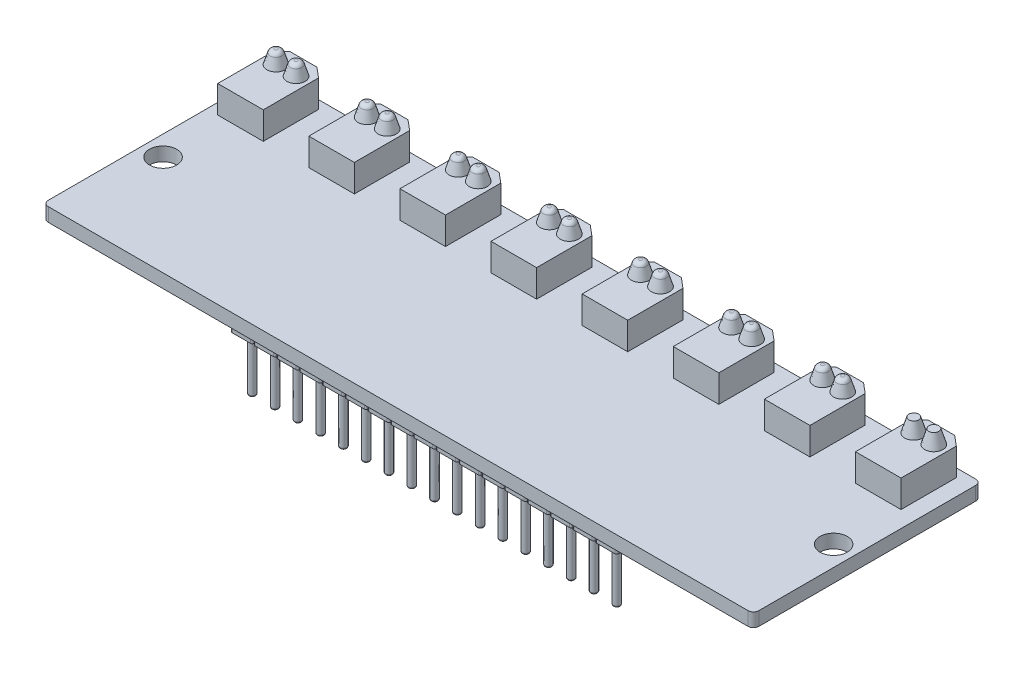
SolidWorks part; units mm, degrees
ref_plane "Front Plane" through (0, 0, 0) normal (0, 0, 1) x (1, 0, 0)
ref_plane "Top Plane" through (0, 0, 0) normal (0, 1, 0) x (1, 0, 0)
ref_plane "Right Plane" through (0, 0, 0) normal (1, 0, 0) x (0, 0, -1)
sketch "Sketch1" plane through (0, 0, 0) normal (0, 1, 0) x (1, 0, 0)
  line L1 (39, -12.5) -> (-39, -12.5)
  line L2 (39, -12.5) -> (39, 12.5)
  line L3 (39, 12.5) -> (-39, 12.5)
  line L4 (-39, -12.5) -> (-39, 12.5)
  line L5 (39, -12.5) -> (-39, 12.5) construction
  line L6 (39, 12.5) -> (-39, -12.5) construction
  point P0 (0, 0)
  dimension "D1" = 25
  dimension "D2" = 78
extrude "Boss-Extrude1" add sketch "Sketch1" along normal blind 1.5
fillet "Fillet1" radius 0.6 4 edges at (39, 0.75, 12.5) (39, 0.75, -12.5) (-39, 0.75, -12.5) (-39, 0.75, 12.5)
sketch "Sketch2" plane through (0, 1.5, 0) normal (0, 1, 0) x (1, 0, 0)
  line L0 (0, 0) -> (0, 12.5) construction
  line L1 (38.4, 12.5) -> (-38.4, 12.5) construction
  line L2 (-39, 11.9) -> (-39, -11.9) construction
  circle A0 centre (-36.8, -1.5) radius 1.5
  circle A1 centre (36.8, -1.5) radius 1.5
  dimension "D1" = 3
  dimension "D2" = 14
  dimension "D3" = 2.2
extrude "Cut-Extrude1" cut sketch "Sketch2" against normal blind 1.5
sketch "Sketch3" plane through (0, 1.5, 0) normal (0, 1, 0) x (1, 0, 0)
  line L0 (38.4, 12.5) -> (-38.4, 12.5) construction
  line L1 (-36.8668, 12.5) -> (-33.914, 12.5)
  line L2 (-37.8, 11.5668) -> (-37.8, 5.5)
  line L3 (-37.8, 5.5) -> (-32.8, 5.5)
  line L4 (-32.8, 11.5668) -> (-32.8, 5.5)
  line L5 (-37.4112, 11.9556) -> (-32.8, 5.5) construction
  line L6 (-37.8, 5.5) -> (-33.217, 11.9161) construction
  line L7 (-39, 11.9) -> (-39, -11.9) construction
  line L8 (-36.8668, 12.5) -> (-37.8, 11.5668)
  line L9 (-33.914, 12.5) -> (-32.8, 11.5668)
  line L10 (-22.8, 11.5668) -> (-22.8, 5.5)
  line L11 (-23.914, 12.5) -> (-22.8, 11.5668)
  line L12 (-26.8668, 12.5) -> (-23.914, 12.5)
  line L13 (-26.8668, 12.5) -> (-27.8, 11.5668)
  line L14 (-27.8, 11.5668) -> (-27.8, 5.5)
  line L15 (-27.8, 5.5) -> (-22.8, 5.5)
  line L16 (-12.8, 11.5668) -> (-12.8, 5.5)
  line L17 (-13.914, 12.5) -> (-12.8, 11.5668)
  line L18 (-16.8668, 12.5) -> (-13.914, 12.5)
  line L19 (-16.8668, 12.5) -> (-17.8, 11.5668)
  line L20 (-17.8, 11.5668) -> (-17.8, 5.5)
  line L21 (-17.8, 5.5) -> (-12.8, 5.5)
  line L22 (-2.8, 11.5668) -> (-2.8, 5.5)
  line L23 (-3.914, 12.5) -> (-2.8, 11.5668)
  line L24 (-6.8668, 12.5) -> (-3.914, 12.5)
  line L25 (-6.8668, 12.5) -> (-7.8, 11.5668)
  line L26 (-7.8, 11.5668) -> (-7.8, 5.5)
  line L27 (-7.8, 5.5) -> (-2.8, 5.5)
  line L28 (7.2, 11.5668) -> (7.2, 5.5)
  line L29 (6.086, 12.5) -> (7.2, 11.5668)
  line L30 (3.1332, 12.5) -> (6.086, 12.5)
  line L31 (3.1332, 12.5) -> (2.2, 11.5668)
  line L32 (2.2, 11.5668) -> (2.2, 5.5)
  line L33 (2.2, 5.5) -> (7.2, 5.5)
  line L34 (17.2, 11.5668) -> (17.2, 5.5)
  line L35 (16.086, 12.5) -> (17.2, 11.5668)
  line L36 (13.1332, 12.5) -> (16.086, 12.5)
  line L37 (13.1332, 12.5) -> (12.2, 11.5668)
  line L38 (12.2, 11.5668) -> (12.2, 5.5)
  line L39 (12.2, 5.5) -> (17.2, 5.5)
  line L40 (27.2, 11.5668) -> (27.2, 5.5)
  line L41 (26.086, 12.5) -> (27.2, 11.5668)
  line L42 (23.1332, 12.5) -> (26.086, 12.5)
  line L43 (23.1332, 12.5) -> (22.2, 11.5668)
  line L44 (22.2, 11.5668) -> (22.2, 5.5)
  line L45 (22.2, 5.5) -> (27.2, 5.5)
  line L46 (37.2, 11.5668) -> (37.2, 5.5)
  line L47 (36.086, 12.5) -> (37.2, 11.5668)
  line L48 (33.1332, 12.5) -> (36.086, 12.5)
  line L49 (33.1332, 12.5) -> (32.2, 11.5668)
  line L50 (32.2, 11.5668) -> (32.2, 5.5)
  line L51 (32.2, 5.5) -> (37.2, 5.5)
  point P0 (-35.3, 9)
  dimension "D1" = 5
  dimension "D2" = 7
  dimension "D3" = 0
  dimension "D4" = 1.2
  dimension "D5" = 8
extrude "Boss-Extrude2" add sketch "Sketch3" along normal blind 3
sketch "Sketch4" plane through (0, 4.5, 0) normal (0, 1, 0) x (1, 0, 0)
  line L0 (-37.8, 11.5668) -> (-37.8, 5.5) construction
  line L1 (-32.8, 5.5) -> (-32.8, 11.5668) construction
  line L2 (-37.8, 5.5) -> (-32.8, 5.5) construction
  line L3 (-37.8, 5.5) -> (-32.8, 5.5) construction
  circle A0 centre (-36.4, 10.4996) radius 1
  circle A1 centre (-34.2, 10.4996) radius 1
  circle A2 centre (-26.4, 10.4996) radius 1 construction
  circle A3 centre (-24.2, 10.4996) radius 1 construction
  circle A4 centre (-16.4, 10.4996) radius 1 construction
  circle A5 centre (-14.2, 10.4996) radius 1 construction
  circle A6 centre (-6.4, 10.4996) radius 1 construction
  circle A7 centre (-4.2, 10.4996) radius 1 construction
  circle A8 centre (3.6, 10.4996) radius 1 construction
  circle A9 centre (5.8, 10.4996) radius 1 construction
  circle A10 centre (13.6, 10.4996) radius 1 construction
  circle A11 centre (15.8, 10.4996) radius 1 construction
  circle A12 centre (23.6, 10.4996) radius 1 construction
  circle A13 centre (25.8, 10.4996) radius 1 construction
  circle A14 centre (33.6, 10.4996) radius 1 construction
  circle A15 centre (35.8, 10.4996) radius 1 construction
  circle A16 centre (-26.4, 10.4996) radius 1
  circle A17 centre (-24.2, 10.4996) radius 1
  circle A18 centre (-16.4, 10.4996) radius 1
  circle A19 centre (-14.2, 10.4996) radius 1
  circle A20 centre (-6.4, 10.4996) radius 1
  circle A21 centre (-4.2, 10.4996) radius 1
  circle A22 centre (3.6, 10.4996) radius 1
  circle A23 centre (5.8, 10.4996) radius 1
  circle A24 centre (13.6, 10.4996) radius 1
  circle A25 centre (15.8, 10.4996) radius 1
  circle A26 centre (23.6, 10.4996) radius 1
  circle A27 centre (25.8, 10.4996) radius 1
  circle A28 centre (33.6, 10.4996) radius 1
  circle A29 centre (35.8, 10.4996) radius 1
  dimension "D1" = 2
  dimension "D2" = 2
  dimension "D5" = 4.9996
  dimension "D6" = 4.9996
  dimension "D3" = 1.4
  dimension "D4" = 1.4
  dimension "D7" = 8
  dimension "D8" = 8
extrude "Boss-Extrude7" add sketch "Sketch4" along normal blind 1.5 draft 17
fillet "Fillet4" radius 0.5 14 edges at (-36.4, 6, -9.9582) (-34.2, 6, -9.9582) (-26.4, 6, -9.9582) (-24.2, 6, -9.9582) (-16.4, 6, -9.9582) (-14.2, 6, -9.9582) (-6.4, 6, -9.9582) (-4.2, 6, -9.9582) (25.8, 6, -9.9582) (23.6, 6, -9.9582) (15.8, 6, -9.9582) (13.6, 6, -9.9582) (5.8, 6, -9.9582) (3.6, 6, -9.9582)
sketch "Sketch5" plane through (0, 0, 0) normal (0, -1, 0) x (1, 0, 0)
  line L0 (38.4, -12.5) -> (-38.4, -12.5) construction
  line L1 (-22.5, 10.9) -> (-20.1, 10.9)
  line L2 (-22.5, 10.9) -> (-22.5, 8.5)
  line L3 (-22.5, 8.5) -> (-20.1, 8.5)
  line L4 (-20.1, 10.9) -> (-20.1, 8.5)
  line L5 (-22.5, 10.9) -> (-20.1, 8.5) construction
  line L6 (-22.5, 8.5) -> (-20.1, 10.9) construction
  line L7 (-20, 10.9) -> (-20, 8.5)
  line L8 (-17.6, 10.9) -> (-17.6, 8.5)
  line L9 (-20, 8.5) -> (-17.6, 8.5)
  line L10 (-17.5, 10.9) -> (-17.5, 8.5)
  line L11 (-15.1, 10.9) -> (-15.1, 8.5)
  line L12 (-17.5, 8.5) -> (-15.1, 8.5)
  line L13 (-15, 10.9) -> (-15, 8.5)
  line L14 (-12.6, 10.9) -> (-12.6, 8.5)
  line L15 (-15, 8.5) -> (-12.6, 8.5)
  line L16 (-12.5, 10.9) -> (-12.5, 8.5)
  line L17 (-10.1, 10.9) -> (-10.1, 8.5)
  line L18 (-12.5, 8.5) -> (-10.1, 8.5)
  line L19 (-10, 10.9) -> (-10, 8.5)
  line L20 (-7.6, 10.9) -> (-7.6, 8.5)
  line L21 (-10, 8.5) -> (-7.6, 8.5)
  line L22 (-7.5, 10.9) -> (-7.5, 8.5)
  line L23 (-5.1, 10.9) -> (-5.1, 8.5)
  line L24 (-7.5, 8.5) -> (-5.1, 8.5)
  line L25 (-5, 10.9) -> (-5, 8.5)
  line L26 (-2.6, 10.9) -> (-2.6, 8.5)
  line L27 (-5, 8.5) -> (-2.6, 8.5)
  line L28 (-2.5, 10.9) -> (-2.5, 8.5)
  line L29 (-0.1, 10.9) -> (-0.1, 8.5)
  line L30 (-2.5, 8.5) -> (-0.1, 8.5)
  line L31 (0, 10.9) -> (0, 8.5)
  line L32 (2.4, 10.9) -> (2.4, 8.5)
  line L33 (0, 8.5) -> (2.4, 8.5)
  line L34 (2.5, 10.9) -> (2.5, 8.5)
  line L35 (4.9, 10.9) -> (4.9, 8.5)
  line L36 (2.5, 8.5) -> (4.9, 8.5)
  line L37 (5, 10.9) -> (5, 8.5)
  line L38 (7.4, 10.9) -> (7.4, 8.5)
  line L39 (5, 8.5) -> (7.4, 8.5)
  line L40 (7.5, 10.9) -> (7.5, 8.5)
  line L41 (9.9, 10.9) -> (9.9, 8.5)
  line L42 (7.5, 8.5) -> (9.9, 8.5)
  line L43 (10, 10.9) -> (10, 8.5)
  line L44 (12.4, 10.9) -> (12.4, 8.5)
  line L45 (10, 8.5) -> (12.4, 8.5)
  line L46 (12.5, 10.9) -> (12.5, 8.5)
  line L47 (14.9, 10.9) -> (14.9, 8.5)
  line L48 (12.5, 8.5) -> (14.9, 8.5)
  line L49 (15, 10.9) -> (15, 8.5)
  line L50 (17.4, 10.9) -> (17.4, 8.5)
  line L51 (15, 8.5) -> (17.4, 8.5)
  line L52 (17.5, 10.9) -> (17.5, 8.5)
  line L53 (19.9, 10.9) -> (19.9, 8.5)
  line L54 (17.5, 8.5) -> (19.9, 8.5)
  line L55 (20, 10.9) -> (20, 8.5)
  line L56 (22.4, 10.9) -> (22.4, 8.5)
  line L57 (20, 8.5) -> (22.4, 8.5)
  line L58 (-20, 10.9) -> (-20, 8.5)
  line L59 (-17.6, 10.9) -> (-17.6, 8.5)
  line L60 (-20, 8.5) -> (-17.6, 8.5)
  line L61 (-20, 10.9) -> (-17.6, 10.9)
  line L62 (-17.5, 10.9) -> (-17.5, 8.5)
  line L63 (-15.1, 10.9) -> (-15.1, 8.5)
  line L64 (-17.5, 8.5) -> (-15.1, 8.5)
  line L65 (-17.5, 10.9) -> (-15.1, 10.9)
  line L66 (-15, 10.9) -> (-15, 8.5)
  line L67 (-12.6, 10.9) -> (-12.6, 8.5)
  line L68 (-15, 8.5) -> (-12.6, 8.5)
  line L69 (-15, 10.9) -> (-12.6, 10.9)
  line L70 (-12.5, 10.9) -> (-12.5, 8.5)
  line L71 (-10.1, 10.9) -> (-10.1, 8.5)
  line L72 (-12.5, 8.5) -> (-10.1, 8.5)
  line L73 (-12.5, 10.9) -> (-10.1, 10.9)
  line L74 (-10, 10.9) -> (-10, 8.5)
  line L75 (-7.6, 10.9) -> (-7.6, 8.5)
  line L76 (-10, 8.5) -> (-7.6, 8.5)
  line L77 (-10, 10.9) -> (-7.6, 10.9)
  line L78 (-7.5, 10.9) -> (-7.5, 8.5)
  line L79 (-5.1, 10.9) -> (-5.1, 8.5)
  line L80 (-7.5, 8.5) -> (-5.1, 8.5)
  line L81 (-7.5, 10.9) -> (-5.1, 10.9)
  line L82 (-5, 10.9) -> (-5, 8.5)
  line L83 (-2.6, 10.9) -> (-2.6, 8.5)
  line L84 (-5, 8.5) -> (-2.6, 8.5)
  line L85 (-5, 10.9) -> (-2.6, 10.9)
  line L86 (-2.5, 10.9) -> (-2.5, 8.5)
  line L87 (-0.1, 10.9) -> (-0.1, 8.5)
  line L88 (-2.5, 8.5) -> (-0.1, 8.5)
  line L89 (-2.5, 10.9) -> (-0.1, 10.9)
  line L90 (0, 10.9) -> (0, 8.5)
  line L91 (2.4, 10.9) -> (2.4, 8.5)
  line L92 (0, 8.5) -> (2.4, 8.5)
  line L93 (0, 10.9) -> (2.4, 10.9)
  line L94 (2.5, 10.9) -> (2.5, 8.5)
  line L95 (4.9, 10.9) -> (4.9, 8.5)
  line L96 (2.5, 8.5) -> (4.9, 8.5)
  line L97 (2.5, 10.9) -> (4.9, 10.9)
  line L98 (5, 10.9) -> (5, 8.5)
  line L99 (7.4, 10.9) -> (7.4, 8.5)
  line L100 (5, 8.5) -> (7.4, 8.5)
  line L101 (5, 10.9) -> (7.4, 10.9)
  line L102 (7.5, 10.9) -> (7.5, 8.5)
  line L103 (9.9, 10.9) -> (9.9, 8.5)
  line L104 (7.5, 8.5) -> (9.9, 8.5)
  line L105 (7.5, 10.9) -> (9.9, 10.9)
  line L106 (10, 10.9) -> (10, 8.5)
  line L107 (12.4, 10.9) -> (12.4, 8.5)
  line L108 (10, 8.5) -> (12.4, 8.5)
  line L109 (10, 10.9) -> (12.4, 10.9)
  line L110 (12.5, 10.9) -> (12.5, 8.5)
  line L111 (14.9, 10.9) -> (14.9, 8.5)
  line L112 (12.5, 8.5) -> (14.9, 8.5)
  line L113 (12.5, 10.9) -> (14.9, 10.9)
  line L114 (15, 10.9) -> (15, 8.5)
  line L115 (17.4, 10.9) -> (17.4, 8.5)
  line L116 (15, 8.5) -> (17.4, 8.5)
  line L117 (15, 10.9) -> (17.4, 10.9)
  line L118 (17.5, 10.9) -> (17.5, 8.5)
  line L119 (19.9, 10.9) -> (19.9, 8.5)
  line L120 (17.5, 8.5) -> (19.9, 8.5)
  line L121 (17.5, 10.9) -> (19.9, 10.9)
  line L122 (20, 10.9) -> (20, 8.5)
  line L123 (22.4, 10.9) -> (22.4, 8.5)
  line L124 (20, 8.5) -> (22.4, 8.5)
  line L125 (20, 10.9) -> (22.4, 10.9)
  line L126 (-39, -11.9) -> (-39, 11.9) construction
  point P0 (-21.3, 9.7)
  dimension "D1" = 2.4
  dimension "D2" = 2.4
  dimension "D3" = 21
  dimension "D6" = 16.5
  dimension "D4" = 18
  dimension "D5" = 18
extrude "Boss-Extrude12" add sketch "Sketch5" along normal blind 2 contours L65 L10 L12 L11 | L69 L13 L15 L14 | L73 L16 L18 L17 | L77 L19 L21 L20 | L81 L22 L24 L23 | L61 L7 L9 L8 | L85 L25 L27 L26 | L89 L28 L30 L29 | L93 L31 L33 L32 | L97 L34 L36 L35 | L101 L37 L39 L38 | L105 L40 L42 L41 | L109 L43 L45 L44 | L113 L46 L48 L47 | L117 L49 L51 L50 | L121 L52 L54 L53 | L125 L55 L57 L56 region at (-18.8, 0, 9.7) region at (-16.3, 0, 9.7) region at (-13.8, 0, 9.7) region at (-11.3, 0, 9.7) region at (-8.8, 0, 9.7) region at (-6.3, 0, 9.7) region at (-3.8, 0, 9.7) region at (-1.3, 0, 9.7) region at (1.2, 0, 9.7) region at (3.7, 0, 9.7) region at (6.2, 0, 9.7) region at (8.7, 0, 9.7) region at (11.2, 0, 9.7) region at (13.7, 0, 9.7) region at (16.2, 0, 9.7) region at (18.7, 0, 9.7) region at (21.2, 0, 9.7)
sketch "Sketch6" plane through (0, -2, 0) normal (0, -1, 0) x (1, 0, 0)
  line L0 (-20, 8.5) -> (-17.6, 8.5) construction
  line L1 (-20, 10.9) -> (-17.6, 10.9) construction
  circle A0 centre (-18.8, 9.7) radius 0.375
  circle A1 centre (-16.3, 9.7) radius 0.375
  circle A2 centre (-13.8, 9.7) radius 0.375
  circle A3 centre (-11.3, 9.7) radius 0.375
  circle A4 centre (-8.8, 9.7) radius 0.375
  circle A5 centre (-6.3, 9.7) radius 0.375
  circle A6 centre (-3.8, 9.7) radius 0.375
  circle A7 centre (-1.3, 9.7) radius 0.375
  circle A8 centre (1.2, 9.7) radius 0.375
  circle A9 centre (3.7, 9.7) radius 0.375
  circle A10 centre (6.2, 9.7) radius 0.375
  circle A11 centre (8.7, 9.7) radius 0.375
  circle A12 centre (11.2, 9.7) radius 0.375
  circle A13 centre (13.7, 9.7) radius 0.375
  circle A14 centre (16.2, 9.7) radius 0.375
  circle A15 centre (18.7, 9.7) radius 0.375
  circle A16 centre (21.2, 9.7) radius 0.375
  point P4 (-18.8, 10.9)
  dimension "D1" = 1.2
  dimension "D2" = 1.2
  dimension "D3" = 0.75
  dimension "D4" = 17
extrude "Boss-Extrude13" add sketch "Sketch6" along normal blind 6
fillet "Fillet5" radius 0.2 4 edges at (-17.6, -1, 10.9) (-17.6, -1, 8.5) (-20, -1, 8.5) (-20, -1, 10.9)
fillet "Fillet7" radius 0.2 64 edges at (22.4, -1, 8.5) (20, -1, 8.5) (19.9, -1, 8.5) (17.5, -1, 8.5) (17.4, -1, 8.5) (15, -1, 8.5) (14.9, -1, 8.5) (12.5, -1, 8.5) (12.4, -1, 8.5) (10, -1, 8.5) (9.9, -1, 8.5) (7.5, -1, 8.5) (7.4, -1, 8.5) (5, -1, 8.5) (4.9, -1, 8.5) (2.5, -1, 8.5) (2.4, -1, 8.5) (0, -1, 8.5) (-0.1, -1, 8.5) (-2.5, -1, 8.5) (-2.6, -1, 8.5) (-5, -1, 8.5) (-5.1, -1, 8.5) (-7.5, -1, 8.5) (-7.6, -1, 8.5) (-10, -1, 8.5) (-10.1, -1, 8.5) (-12.5, -1, 8.5) (-12.6, -1, 8.5) (-15, -1, 8.5) (-15.1, -1, 8.5) (-17.5, -1, 8.5) (22.4, -1, 10.9) (20, -1, 10.9) (19.9, -1, 10.9) (17.5, -1, 10.9) (17.4, -1, 10.9) (15, -1, 10.9) (14.9, -1, 10.9) (12.5, -1, 10.9) (12.4, -1, 10.9) (10, -1, 10.9) (9.9, -1, 10.9) (7.5, -1, 10.9) (7.4, -1, 10.9) (5, -1, 10.9) (4.9, -1, 10.9) (2.5, -1, 10.9) (2.4, -1, 10.9) (0, -1, 10.9) (-0.1, -1, 10.9) (-2.5, -1, 10.9) (-2.6, -1, 10.9) (-5, -1, 10.9) (-5.1, -1, 10.9) (-7.5, -1, 10.9) (-7.6, -1, 10.9) (-10, -1, 10.9) (-10.1, -1, 10.9) (-12.5, -1, 10.9) (-12.6, -1, 10.9) (-15, -1, 10.9) (-15.1, -1, 10.9) (-17.5, -1, 10.9)
fillet "Fillet8" radius 0.2 17 edges at (21.2, -8, 9.325) (18.7, -8, 9.325) (16.2, -8, 9.325) (13.7, -8, 9.325) (11.2, -8, 9.325) (8.7, -8, 9.325) (6.2, -8, 9.325) (3.7, -8, 9.325) (1.2, -8, 9.325) (-1.3, -8, 9.325) (-3.8, -8, 9.325) (-6.3, -8, 9.325) (-8.8, -8, 9.325) (-11.3, -8, 9.325) (-13.8, -8, 9.325) (-16.3, -8, 9.325) (-18.8, -8, 9.325)
